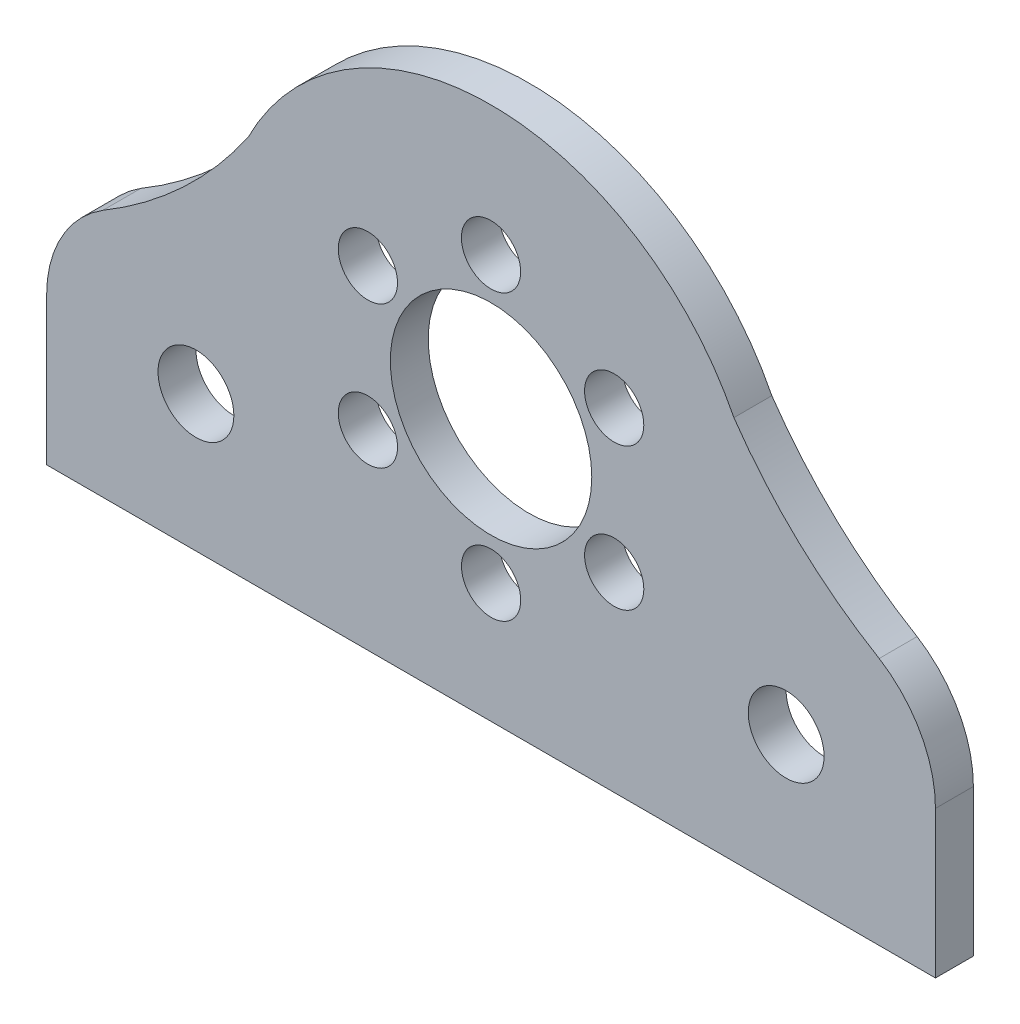
SolidWorks part; units mm, degrees
ref_plane "Alzado" through (0, 0, 0) normal (0, 0, 1) x (1, 0, 0)
ref_plane "Planta" through (0, 0, 0) normal (0, 1, 0) x (1, 0, 0)
ref_plane "Vista lateral" through (0, 0, 0) normal (1, 0, 0) x (0, 0, -1)
sketch "Croquis1" plane through (0, 0, 0) normal (0, 0, 1) x (1, 0, 0)
  line L4 (0, 0) -> (0, 1.5946) construction
  line L17 (-18.75, -11.05) -> (18.75, -11.05)
  line L18 (0, -11.05) -> (0, -9.9022) construction
  line L21 (-18.75, -11.05) -> (-18.75, -4.8527)
  line L23 (18.75, -11.05) -> (18.75, -4.8527)
  line L25 (0, 11.4788) -> (0, -11.05) construction
  circle A8 centre (0, 0) radius 4.25
  circle A12 centre (-0.0012, 5.9988) radius 1.25
  circle A13 centre (5.1945, 3.0004) radius 1.25
  circle A14 centre (5.1957, -2.9984) radius 1.25
  circle A15 centre (0.0012, -5.9988) radius 1.25
  circle A16 centre (-5.1945, -3.0004) radius 1.25
  circle A17 centre (-5.1957, 2.9984) radius 1.25
  circle A19 centre (12.45, -5.3) radius 1.6
  circle A21 centre (-12.45, -5.3) radius 1.6
  arc A23 (10.2473, 5.1727) -> (-10.2473, 5.1727) centre (0, 0) ccw
  arc A32 (-18.75, -4.8527) -> (-16.3755, -0.5624) centre (-13.6868, -4.8527) cw
  arc A33 (-16.3755, -0.5624) -> (-10.2473, 5.1727) centre (-26.2731, 16.1553) ccw
  arc A34 (16.3755, -0.5624) -> (10.2473, 5.1727) centre (26.2731, 16.1553) cw
  arc A35 (18.75, -4.8527) -> (16.3755, -0.5624) centre (13.6868, -4.8527) ccw
  point P29 (-11.465, -0.5624)
  point P34 (11.465, -0.5624)
  dimension "D1" = 12.45
  dimension "D2" = 37.5
  dimension "D7" = 3.2
  dimension "D4" = 5.3
  dimension "D5" = 11.05
  dimension "D6" = 8.5
  dimension "D3" = 2.5
  dimension "D9" = 11.4788
extrude "Saliente-Extruir1" add sketch "Croquis1" along normal blind 1.6 contours A21 A19 A17 A16 A15 A14 A13 A12 A8 region at (-18.3125, -7.9514, 0)
